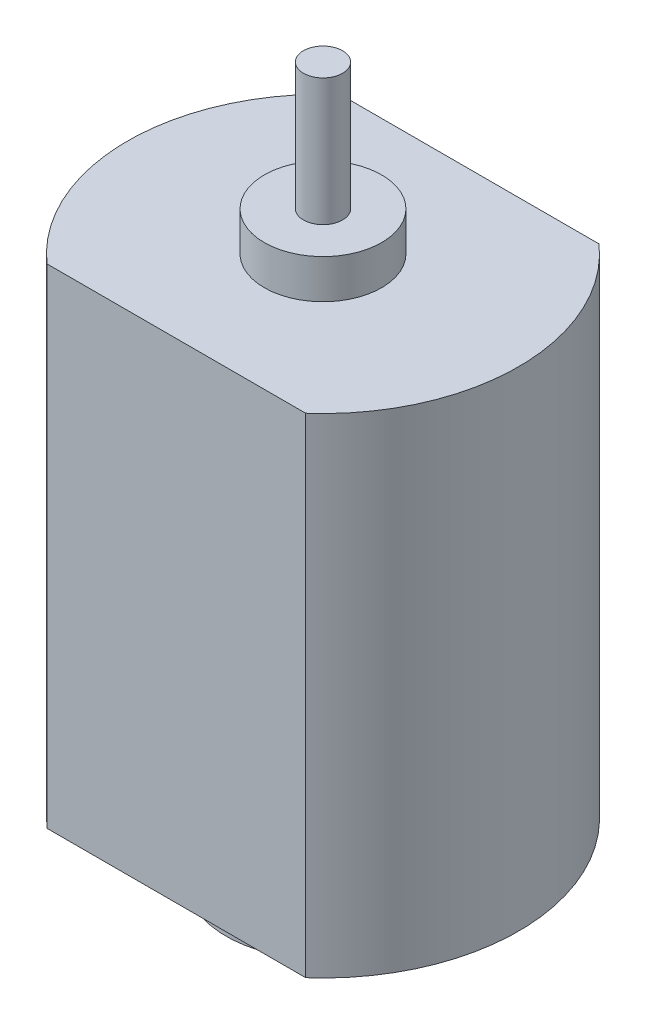
SolidWorks part; units mm, degrees
ref_plane "Front Plane" through (0, 0, 0) normal (0, 0, 1) x (1, 0, 0)
ref_plane "Top Plane" through (0, 0, 0) normal (0, 1, 0) x (1, 0, 0)
ref_plane "Right Plane" through (0, 0, 0) normal (1, 0, 0) x (0, 0, -1)
sketch "Sketch1" plane through (0, 0, 0) normal (0, 1, 0) x (1, 0, 0)
  line L2 (-6.6144, -7.5) -> (6.6144, -7.5)
  line L3 (-6.6144, 7.5) -> (6.6144, 7.5)
  circle A0 centre (0, 0) radius 10
  circle A1 centre (0, 0) radius 3
  circle A2 centre (0, 0) radius 1
  dimension "D2" = 2
  dimension "D3" = 6
  dimension "D4" = 20
  dimension "D1" = 15
extrude "Boss-Extrude1" add sketch "Sketch1" against normal blind 25 contours L2 A0 L3 A1 | A2 | A1 A2 region at (-9.75, 0, 0) region at (-2.9151, 0, 0) region at (0, 0, 0)
extrude "Boss-Extrude2" add sketch "Sketch1<3>" along normal blind 2 contours A1 A2 | A2 region at (-2.9151, 0, 0)
sketch "Sketch1<3>" plane through (0, 0, 0) normal (0, 1, 0) x (1, 0, 0) same geometry as "Sketch1"
extrude "Boss-Extrude3" add sketch "Sketch1<4>" along normal blind 8.5 contours A2 | A2 region at (0, 0, 0)
sketch "Sketch1<4>" plane through (0, 0, 0) normal (0, 1, 0) x (1, 0, 0) same geometry as "Sketch1"
sketch "Sketch2" plane through (0, -25, 0) normal (0, -1, 0) x (1, 0, 0)
  line L0 (-2.846, -4.05) -> (2.846, -4.05)
  line L1 (0, -4.05) -> (0, 4.95)
  circle A0 centre (0, 0) radius 4.95
  dimension "D1" = 9.9
  dimension "D2" = 9
extrude "Boss-Extrude4" add sketch "Sketch2" along normal blind 2.75 contours L1 A0 L0 | L0 A0 L1 region at (-2.1491, -25, 0.2091) region at (2.1491, -25, 0.2091)
